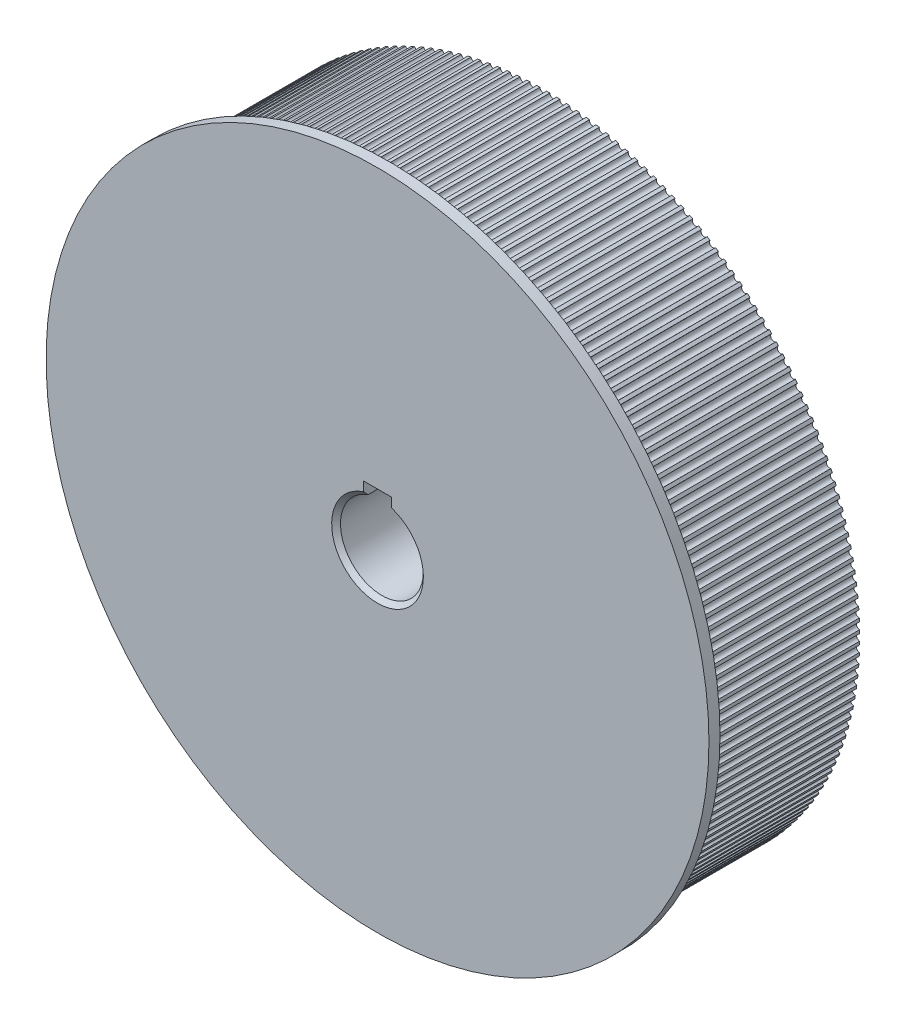
SolidWorks part; units mm, degrees
ref_plane "Přední rovina" through (0, 0, 0) normal (0, 0, 1) x (1, 0, 0)
ref_plane "Horní rovina" through (0, 0, 0) normal (0, 1, 0) x (1, 0, 0)
ref_plane "Pravá rovina" through (0, 0, 0) normal (1, 0, 0) x (0, 0, -1)
sketch "Skica1" plane through (0, 0, 0) normal (0, 0, 1) x (1, 0, 0)
  line L0 (-0.9, 57.2894) -> (0, 0) construction
  line L1 (0, 0) -> (0.9, 57.2894) construction
  line L2 (-0.9, 57.2894) -> (0.9, 57.2894) construction
  line L3 (-0.9, 57.2894) -> (-0.1178, 7.4991)
  line L5 (0.1178, 7.4991) -> (0.9, 57.2894)
  circle A0 centre (0, 0) radius 57.2965 construction
  arc A1 (-0.6, 57.2934) -> (0.6, 57.2934) centre (0, 57.2965) ccw
  arc A2 (-0.9, 57.2894) -> (-0.6, 57.2934) centre (0, 0) cw
  arc A3 (0.9, 57.2894) -> (0.6, 57.2934) centre (0, 0) ccw
  circle A4 centre (0, 0) radius 7.5 construction
  arc A5 (-0.1178, 7.4991) -> (0.1178, 7.4991) centre (0, 0) cw
  point P4 (0, 57.2894)
  dimension "D3" = 15
  dimension "D1" = 0.3
  dimension "D2" = 1.2
  dimension "D4" = 1.8
extrude "Přidat vysunutím1" add sketch "Skica1" along normal mid plane 30
pattern_circular "Kruhové pole1" count 200 over 360 about axis through (0, 0, 15) along (0, 0, -1) of "Přidat vysunutím1"
sketch "Skica2" plane through (0, 0, 15) normal (0, 0, 1) x (1, 0, 0)
  line L0 (0, 0) -> (0, 7.0711) construction
  line L1 (-2.5, 7.0711) -> (2.5, 7.0711)
  line L2 (-2.5, 7.0711) -> (-2.5, 9.6)
  line L3 (-2.5, 9.6) -> (2.5, 9.6)
  line L4 (2.5, 7.0711) -> (2.5, 9.6)
  circle A1 centre (0, 0) radius 7.5 construction
  dimension "D2" = 2.1
  dimension "D1" = 5
extrude "Odebrat vysunutím1" cut sketch "Skica2" against normal through all
chamfer "Zkosení1" distance 0.8 angle 45 2 edges at (0, -7.5, 15) (0, -7.5, -15)
sketch "Skica3" plane through (0, 0, 15) normal (0, 0, 1) x (1, 0, 0)
  line L0 (2.5, 7.9145) -> (2.5, 9.6) construction
  line L1 (2.5, 9.6) -> (-2.5, 9.6) construction
  line L2 (-2.5, 9.6) -> (-2.5, 7.9145) construction
  line L3 (2.5, 7.9145) -> (2.5, 9.6)
  line L4 (2.5, 9.6) -> (-2.5, 9.6)
  line L5 (-2.5, 9.6) -> (-2.5, 7.9145)
  circle A0 centre (0, 0) radius 60
  arc A1 (-2.5, 7.9145) -> (2.5, 7.9145) centre (0, 0) ccw construction
  arc A2 (-2.5, 7.9145) -> (2.5, 7.9145) centre (0, 0) ccw
  dimension "D1" = 120
extrude "Přidat vysunutím2" add sketch "Skica3" against normal blind 2 contours A0 | L3 L4 L5 A2
